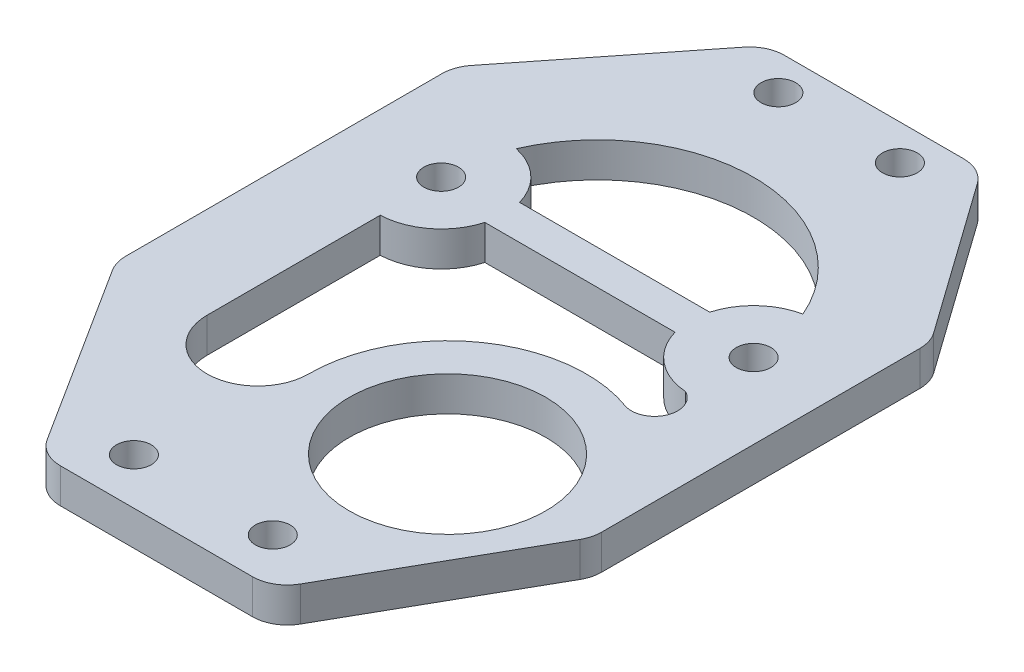
SolidWorks part; units mm, degrees
note: The reader was unsure of these and kept them because the rebuilt part matched: thickness of "Base-Flange1", "Sheet-Metal1", "Sac-Levha2".
ref_plane "Front Plane" through (0, 0, 0) normal (0, 0, 1) x (1, 0, 0)
ref_plane "Top Plane" through (0, 0, 0) normal (0, 1, 0) x (1, 0, 0)
ref_plane "Right Plane" through (0, 0, 0) normal (1, 0, 0) x (0, 0, -1)
sketch "Sketch1" plane through (0, 0, 0) normal (0, 1, 0) x (1, 0, 0)
  line L0 (0, 34.5262) -> (0, -34.5262) construction
  line L1 (-42.1133, 0) -> (42.1133, 0) construction
  line L2 (19.6094, -14.0594) -> (10.8621, -29.4802)
  line L3 (-7.7982, 31) -> (7.7021, 31)
  line L5 (-8.3526, -31) -> (8.2527, -31)
  line L6 (20, 14.9247) -> (20, -12.5792)
  line L7 (13.5, 7.05) -> (-13.5, 7.05) construction
  line L8 (10.147, 29.7386) -> (19.4449, 16.6633)
  line L9 (-13.2814, 0) -> (-13.2814, 1.568)
  line L10 (-8.2227, 8.55) -> (8.2085, 8.55)
  line L11 (-20.564, 16.7008) -> (-10.1508, 29.8615)
  line L12 (-21.2114, 14.8393) -> (-21.2114, -12.4977)
  line L13 (-13.2814, -13.4) -> (-13.2814, 0)
  line L14 (-20.7429, -14.1076) -> (-10.884, -29.6099)
  line L15 (-8.2227, 5.55) -> (8.2085, 5.55)
  circle A0 centre (7.5, -13.4) radius 8.5
  circle A1 centre (6, -27) radius 1.5
  circle A2 centre (-6, -27) radius 1.5
  arc A3 (11.6553, -2.1424) -> (13.1131, 1.5636) centre (12.21, -0.2209) ccw
  arc A4 (11.6553, -2.1424) -> (-4.5, -13.4) centre (7.5, -13.4) ccw
  arc A5 (-13.2814, -13.4) -> (-4.5, -13.4) centre (-8.8907, -13.4) ccw
  circle A6 centre (5.25, 27.9408) radius 1.5
  circle A7 centre (-5.25, 27.9408) radius 1.5
  circle A8 centre (13.5, 7.05) radius 1.5
  arc A9 (12.3796, 12.4347) -> (8.2085, 8.55) centre (13.5, 7.05) ccw
  arc A11 (12.3796, 12.4347) -> (-12.3852, 12.4219) centre (0, 7.05) ccw
  circle A12 centre (-13.5, 7.05) radius 1.5
  arc A13 (-13.2814, 1.568) -> (-8.2227, 5.55) centre (-13.5, 7.05) ccw
  arc A14 (-10.1508, 29.8615) -> (-7.7982, 31) centre (-7.7982, 28) cw
  arc A15 (-21.2114, -12.4977) -> (-20.7429, -14.1076) centre (-18.2114, -12.4977) ccw
  arc A16 (-21.2114, 14.8393) -> (-20.564, 16.7008) centre (-18.2114, 14.8393) cw
  arc A17 (-10.884, -29.6099) -> (-8.3526, -31) centre (-8.3526, -28) ccw
  arc A18 (10.8621, -29.4802) -> (8.2527, -31) centre (8.2527, -28) cw
  arc A19 (19.6094, -14.0594) -> (20, -12.5792) centre (17, -12.5792) ccw
  arc A20 (19.4449, 16.6633) -> (20, 14.9247) centre (17, 14.9247) cw
  arc A21 (10.147, 29.7386) -> (7.7021, 31) centre (7.7021, 28) ccw
  arc A22 (-8.2227, 8.55) -> (-12.3852, 12.4219) centre (-13.5, 7.05) ccw
  arc A23 (8.2085, 5.55) -> (13.1131, 1.5636) centre (13.5, 7.05) ccw
  point P0 (0, 0)
  point P4 (0, 0)
  point P8 (0, 0)
  point P36 (-9.25, 31)
  point P50 (-10, -31)
  point P53 (10, -31)
  point P56 (20, -13.3709)
  point P61 (9.25, 31)
  dimension "D2" = 17.6
  dimension "D4" = 17
  dimension "D5" = 4
  dimension "D9" = 62
  dimension "D10" = 20.45
  dimension "D12" = 13.15
  dimension "D14" = 4
  dimension "D15" = 12
  dimension "D16" = 10.5
  dimension "D18" = 3
  dimension "D19" = 13.5
  dimension "D20" = 11
  dimension "D22" = 4
  dimension "D24" = 3
  dimension "D25" = 3
  dimension "D3" = 7.5
  dimension "D6" = 4
  dimension "D7" = 6
  dimension "D8" = 12
  dimension "D11" = 4
  dimension "D13" = 4.71
  dimension "D17" = 5.25
  dimension "D21" = 7.93
  dimension "D23" = 6.5
base flange "Base-Flange1" sketch "Sketch1" thickness 3 reverse thickness direction yes parameters "D1"=0.7366
scale "Ölçek1" scale about centroid uniform scaling yes scale factor 2
sketch "Bend-Lines1" [suppressed] plane through (0, 0, 0) normal (0, 1, 0) x (1, 0, 0)
sketch "Bounding-Box1" [suppressed] plane through (0, 0, 0) normal (0, 1, 0) x (1, 0, 0)
sheet metal parameters "Sheet-Metal1" thickness 3 parameters "D1"=0.7366
flat pattern "Flat-Pattern1" [suppressed]
sketch "Bend-Lines2" plane through (0, 0, 0) normal (0, 1, 0) x (1, 0, 0)
sketch3d "Bounding-Box2" [suppressed]
  line L0 (13.4132, -59, 0) -> (13.4132, 3, 0) construction
  line L1 (-27.7982, -59, 0) -> (-27.7982, 3, 0) construction
  line L2 (13.4132, -59, 0) -> (-27.7982, -59, 0) construction
  line L3 (13.4132, 3, 0) -> (-27.7982, 3, 0) construction
sheet metal parameters "Sac-Levha2" thickness 3 parameters "D1"=0.7366
flat pattern "Flat-Pattern1"
sketch "Bend-Lines2" plane through (0, 0, 0) normal (0, 1, 0) x (1, 0, 0)
sketch3d "Bounding-Box2" [suppressed]
  line L0 (13.4132, -59, 0) -> (13.4132, 3, 0) construction
  line L1 (-27.7982, -59, 0) -> (-27.7982, 3, 0) construction
  line L2 (13.4132, -59, 0) -> (-27.7982, -59, 0) construction
  line L3 (13.4132, 3, 0) -> (-27.7982, 3, 0) construction
